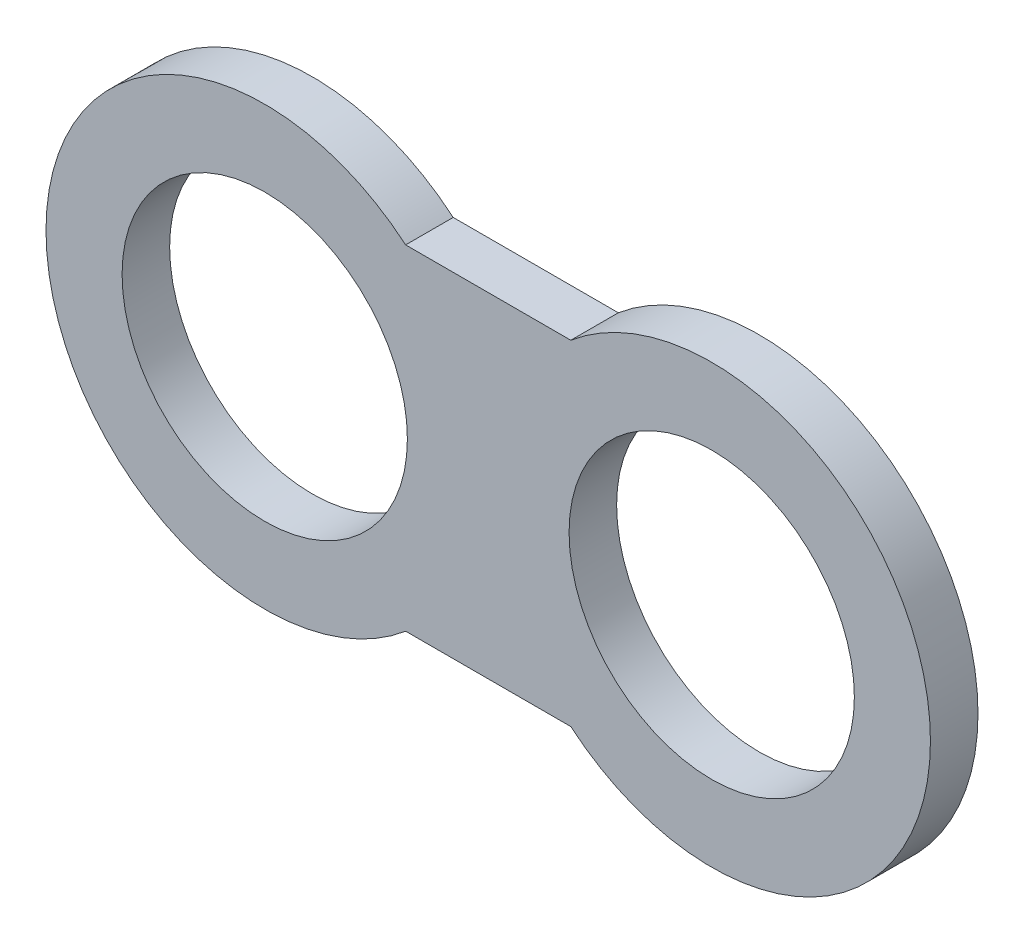
SolidWorks part; units mm, degrees
ref_plane "Front Plane" through (0, 0, 0) normal (0, 0, 1) x (1, 0, 0)
ref_plane "Top Plane" through (0, 0, 0) normal (0, 1, 0) x (1, 0, 0)
ref_plane "Right Plane" through (0, 0, 0) normal (1, 0, 0) x (0, 0, -1)
sketch "Sketch3" plane through (0, 0, 0) normal (0, 0, 1) x (1, 0, 0)
  line L0 (0, 0) -> (-250, 0) construction
  line L1 (650.4122, 0) -> (-650.4122, 0) construction
  dimension "D1" = 250
sketch "Sketch4" plane through (0, 0, 0) normal (0, 0, 1) x (1, 0, 0)
  line L0 (0, 0) -> (220, 0) construction
  line L1 (0, 0) -> (0, 175.9092) construction
  line L2 (0, -55) -> (0, 55) construction
  line L3 (0, 175.9092) -> (0, 0) construction
  line L4 (0, 175.9092) -> (-101.8246, 175.9092)
  line L5 (-101.8246, 175.9092) -> (71.8246, 175.9092)
  line L6 (0, 0) -> (0, -175.9092) construction
  line L7 (0, -175.9092) -> (71.8246, -175.9092)
  line L8 (71.8246, -175.9092) -> (-101.8246, -175.9092)
  circle A0 centre (-250, 0) radius 230
  circle A1 centre (220, 0) radius 230
  circle A2 centre (-250, 0) radius 150
  circle A3 centre (220, 0) radius 150
  dimension "D1" = 220
  dimension "D4" = 300
  dimension "D5" = 300
  dimension "D6" = 460
  dimension "D7" = 460
  dimension "D2" = 173.6492
  dimension "D3" = 173.6492
extrude "Boss-Extrude1" add sketch "Sketch4" along normal blind 25 and the other way blind 25 contours A0 A2 | A1 A3 | A1 L5 L4 A0 L8 L7 region at (-15, 0, 0) region at (-47.3555, 94.2606, 0) region at (314.2606, 202.6445, 0)
extrude "Boss-Extrude2" add sketch "Sketch4<4>" against normal blind 25 contours A0 A2 region at (-47.3555, 94.2606, 0)
sketch "Sketch4<4>" plane through (0, 0, 0) normal (0, 0, 1) x (1, 0, 0) same geometry as "Sketch4"
